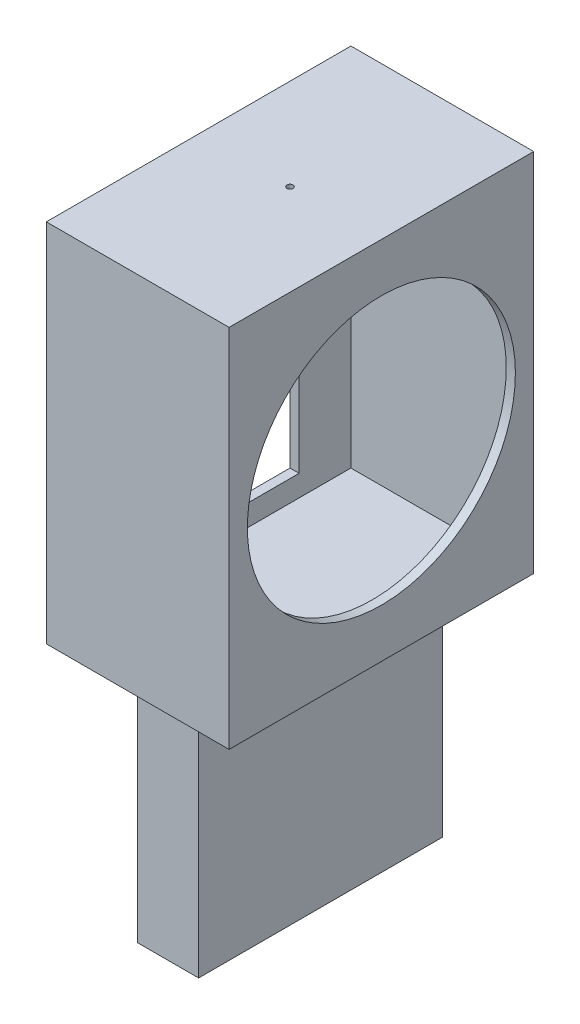
SolidWorks part; units mm, degrees
ref_plane "Front Plane" through (0, 0, 0) normal (0, 0, 1) x (1, 0, 0)
ref_plane "Top Plane" through (0, 0, 0) normal (0, 1, 0) x (1, 0, 0)
ref_plane "Right Plane" through (0, 0, 0) normal (1, 0, 0) x (0, 0, -1)
other "Configuration Table"
sketch "Sketch1" plane through (0, 0, 0) normal (1, 0, 0) x (0, 0, -1)
  line L1 (50, 80) -> (-50, 80)
  line L2 (50, 80) -> (50, 200)
  line L3 (50, 200) -> (-50, 200)
  line L4 (-50, 80) -> (-50, 200)
  line L5 (50, 80) -> (-50, 200) construction
  line L6 (50, 200) -> (-50, 80) construction
extrude "outer" add sketch "Sketch1" along normal blind 60 from offset 98 separate body
sketch "Sketch2" plane through (0, 0, 0) normal (1, 0, 0) x (0, 0, -1)
  line L1 (47, 83) -> (-47, 83)
  line L2 (47, 83) -> (47, 197)
  line L3 (47, 197) -> (-47, 197)
  line L4 (-47, 83) -> (-47, 197)
  line L5 (47, 83) -> (-47, 197) construction
  line L6 (47, 197) -> (-47, 83) construction
extrude "inner" add sketch "Sketch2" along normal blind 54 from offset 101 separate body
sketch "Sketch3" plane through (0, 0, 0) normal (1, 0, 0) x (0, 0, -1)
  line L1 (30, 90) -> (-30, 90)
  line L2 (30, 90) -> (30, 190)
  line L3 (30, 190) -> (-30, 190)
  line L4 (-30, 90) -> (-30, 190)
  line L5 (30, 90) -> (-30, 190) construction
  line L6 (30, 190) -> (-30, 90) construction
extrude "throat_port" add sketch "Sketch3" along normal blind 5 from offset 97 separate body
sketch "Sketch4" plane through (0, 0, 0) normal (1, 0, 0) x (0, 0, -1)
  circle A0 centre (0, 140) radius 44
extrude "fan_port" add sketch "Sketch4" along normal blind 5 from offset 154 separate body
sketch "Sketch5" plane through (0, 0, 0) normal (0, 1, 0) x (1, 0, 0)
  circle A0 centre (128, 0) radius 1
extrude "tc_port" add sketch "Sketch5" along normal blind 5 from offset 196 separate body
combine bodies "Combine1" operation type subtract main body 102 bodies to subtract 103 104 105 106
sketch "Sketch6" plane through (0, 0, 0) normal (1, 0, 0) x (0, 0, -1)
  line L0 (-50, 80) -> (50, 80) construction
  line L1 (40, 0) -> (-40, 0)
  line L2 (40, 0) -> (40, 80)
  line L3 (40, 80) -> (-40, 80)
  line L4 (-40, 0) -> (-40, 80)
  line L5 (40, 0) -> (-40, 80) construction
  line L6 (40, 80) -> (-40, 0) construction
  point P0 (0, 40)
extrude "plenum_stand" add sketch "Sketch6" along normal blind 20 from offset 118 separate body
